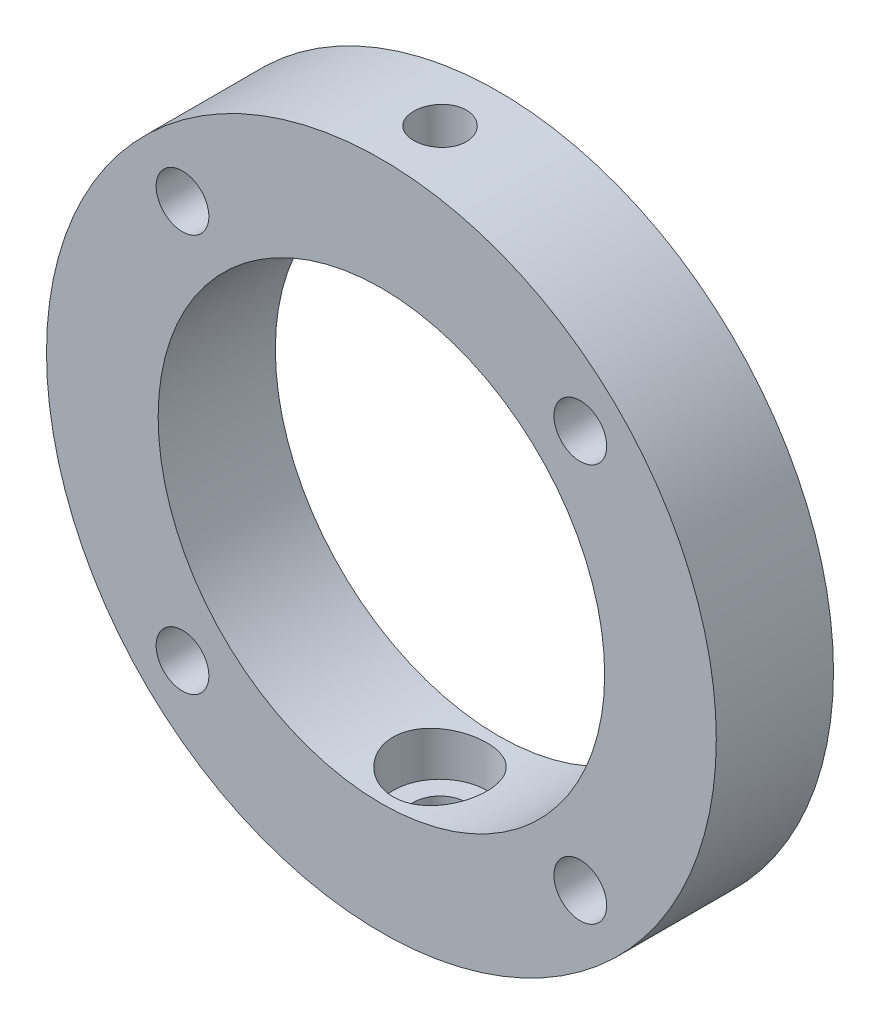
SolidWorks part; units mm, degrees
ref_plane "Front Plane" through (0, 0, 0) normal (0, 0, 1) x (1, 0, 0)
ref_plane "Top Plane" through (0, 0, 0) normal (0, 1, 0) x (1, 0, 0)
ref_plane "Right Plane" through (0, 0, 0) normal (1, 0, 0) x (0, 0, -1)
sketch "Sketch1" plane through (0, 0, 0) normal (0, 0, 1) x (1, 0, 0)
  circle A0 centre (0, 0) radius 28.575
  dimension "D1" = 57.15
extrude "Boss-Extrude1" add sketch "Sketch1" along normal blind 10
sketch "Sketch2" plane through (0, 0, 10) normal (0, 0, 1) x (1, 0, 0)
  circle A0 centre (0, 0) radius 19.05
  dimension "D1" = 38.1
extrude "Cut-Extrude1" cut sketch "Sketch2" against normal through all
ref_plane "Plane1" through (0, 28.575, 0) normal (0, 1, 0) x (1, 0, 0)
sketch "Sketch5" plane through (0, 28.575, 0) normal (0, 1, 0) x (1, 0, 0)
  circle A0 centre (0, -5) radius 2.25
  dimension "D2" = 4.5
  dimension "D1" = 5
extrude "Cut-Extrude2" cut sketch "Sketch5" against normal through all
sketch "Sketch6" plane through (0, 0, 10) normal (0, 0, 1) x (1, 0, 0)
  line L0 (0, 28.575) -> (0, -28.575) construction
  line L1 (5.5, 28.575) -> (-5.5, 28.575) construction
  line L2 (0, 0) -> (-16.9706, 16.9706) construction
  circle A1 centre (0, 0) radius 28.575 construction
  circle A3 centre (0, 0) radius 24 construction
  circle A4 centre (-16.9706, 16.9706) radius 2.25
  circle A5 centre (16.9706, 16.9706) radius 2.25
  circle A6 centre (16.9706, -16.9706) radius 2.25
  circle A7 centre (-16.9706, -16.9706) radius 2.25
  point P21 (0, 0)
  dimension "D2" = 45
  dimension "D1" = 48
  dimension "D3" = 4.5
  dimension "D4" = 4
extrude "Cut-Extrude3" cut sketch "Sketch6" against normal through all
ref_plane "Offset to Inner Ring" through (0, 18.575, 0) normal (0, 1, 0) x (1, 0, 0)
sketch "Sketch7" plane through (0, 28.575, 0) normal (0, 1, 0) x (1, 0, 0)
  circle A0 centre (0, -5) radius 4
  circle A3 centre (0, -5) radius 2.25
  circle A5 centre (0, -5) radius 2.25 construction
  dimension "D1" = 8
ref_plane "Other Side Plane" through (0, -18.575, 0) normal (0, 1, 0) x (1, 0, 0)
extrude "Cut-Extrude5" cut sketch "Sketch7" along normal blind 4 from surface starting at plane "Offset to Inner Ring"
extrude "Cut-Extrude6" cut sketch "Sketch7<4>" against normal blind 4 from surface starting at plane "Other Side Plane"
sketch "Sketch7<4>" plane through (0, 28.575, 0) normal (0, 1, 0) x (1, 0, 0) same geometry as "Sketch7"
